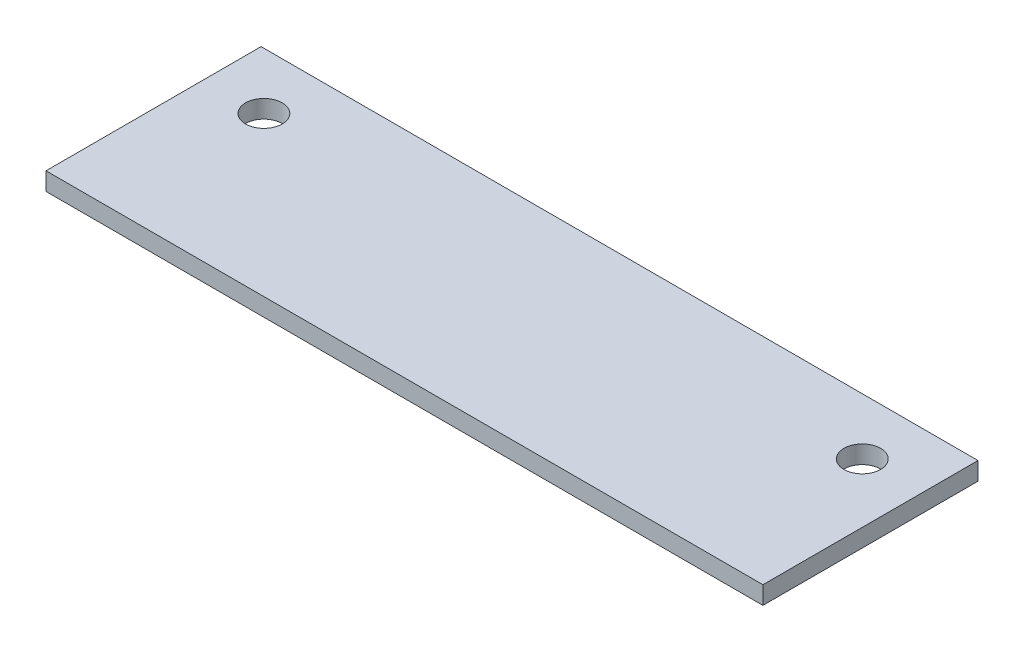
SolidWorks part; units mm, degrees
material "AISI 4130 Steel, annealed at 865C"
ref_plane "X-Y Datum" through (0, 0, 0) normal (0, 0, 1) x (1, 0, 0)
ref_plane "X-Z Datum" through (0, 0, 0) normal (0, 1, 0) x (1, 0, 0)
ref_plane "Y-Z Datum" through (0, 0, 0) normal (1, 0, 0) x (0, 0, -1)
sketch "Sketch1" plane through (0, 0, 0) normal (0, 1, 0) x (1, 0, 0)
  line L1 (-63.5, -38.1) -> (63.5, -38.1)
  line L2 (-63.5, -38.1) -> (-63.5, 38.1)
  line L3 (-63.5, 38.1) -> (63.5, 38.1)
  line L4 (63.5, -38.1) -> (63.5, 38.1)
  line L5 (-63.5, -38.1) -> (63.5, 38.1) construction
  line L6 (-63.5, 38.1) -> (63.5, -38.1) construction
  point P0 (0, 0)
  dimension "D1" = 127
  dimension "D2" = 76.2
extrude "Boss-Extrude1" add sketch "Sketch1" along normal blind 3.175 contours L3 L4 L1 L2
sketch "Sketch3" plane through (0, 3.175, 0) normal (0, 1, 0) x (1, 0, 0)
  line L0 (63.5, 0) -> (-63.5, 0)
  line L4 (-63.5, 38.1) -> (-63.5, -38.1)
  line L5 (-63.5, -38.1) -> (63.5, -38.1)
  line L6 (63.5, -38.1) -> (63.5, 38.1)
  line L7 (63.5, 38.1) -> (-63.5, 38.1)
  line L8 (-63.5, 38.1) -> (-63.5, -38.1)
  line L9 (-63.5, -38.1) -> (63.5, -38.1)
  line L10 (63.5, -38.1) -> (63.5, 38.1)
  line L11 (63.5, 38.1) -> (-63.5, 38.1)
  circle A0 centre (53, 28.1) radius 3.25 construction
  circle A1 centre (-53, 28.1) radius 3.25 construction
  circle A2 centre (53, 28.1) radius 3.25
  circle A3 centre (-53, 28.1) radius 3.25
  line M5 (-63.5, 38.1) -> (-63.5, -38.1)
  line M6 (-63.5, -38.1) -> (63.5, -38.1)
  line M7 (63.5, -38.1) -> (63.5, 38.1)
  dimension "D1" = 0
extrude "Cut-Extrude1" cut sketch "Sketch3" against normal through all contours L0 M7 M5 M6 | A3 | A2 region at (0, 3.175, 19.05) region at (53, 3.175, -28.1) region at (-53, 3.175, -28.1)
